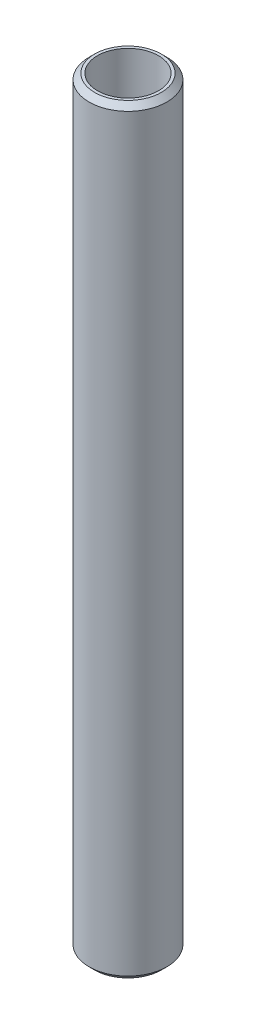
SolidWorks part; units mm, degrees
ref_plane "Front Plane" through (0, 0, 0) normal (0, 0, 1) x (1, 0, 0)
ref_plane "Top Plane" through (0, 0, 0) normal (0, 1, 0) x (1, 0, 0)
ref_plane "Right Plane" through (0, 0, 0) normal (1, 0, 0) x (0, 0, -1)
sketch "Sketch1" plane through (0, 0, 0) normal (0, 1, 0) x (1, 0, 0)
  circle A0 centre (0, 0) radius 20
  dimension "SHAFT_OD" = 40
extrude "Boss-Extrude1" add sketch "Sketch1" along normal blind 390.9582
sketch "Sketch2" plane through (0, 0, 0) normal (0, 1, 0) x (1, 0, 0)
  circle A0 centre (0, 0) radius 15.6857
  dimension "BORE_D" = 31.3713
extrude "Cut-Extrude1" cut sketch "Sketch2" along normal through all
chamfer "Chamfer1" distance 2.8534 angle 45 2 edges at (0, 390.9582, 20) (0, 0, 20)
